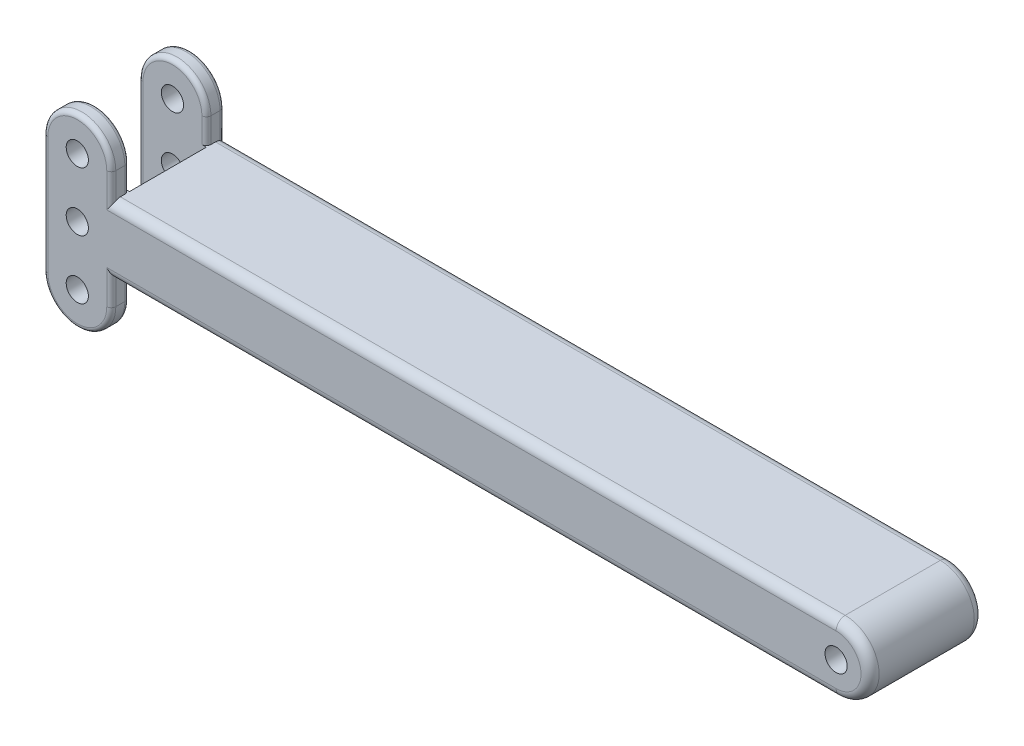
SolidWorks part; units mm, degrees
ref_plane "Front Plane" through (0, 0, 0) normal (0, 0, 1) x (1, 0, 0)
ref_plane "Top Plane" through (0, 0, 0) normal (0, 1, 0) x (1, 0, 0)
ref_plane "Right Plane" through (0, 0, 0) normal (1, 0, 0) x (0, 0, -1)
sketch "Sketch1" plane through (0, 0, 0) normal (0, 0, 1) x (1, 0, 0)
  line L0 (0, 0) -> (0, 33.02) construction
  line L1 (-9.525, 0) -> (-9.525, 33.02)
  line L2 (9.525, 0) -> (9.525, 33.02)
  line L3 (9.525, 26.035) -> (212.725, 26.035)
  line L4 (9.525, 6.985) -> (212.725, 6.985)
  line L5 (0, 16.51) -> (9.525, 26.035) construction
  line L6 (0, 16.51) -> (9.525, 6.985) construction
  arc A0 (-9.525, 0) -> (9.525, 0) centre (0, 0) ccw
  arc A1 (9.525, 33.02) -> (-9.525, 33.02) centre (0, 33.02) ccw
  arc A2 (212.725, 26.035) -> (212.725, 6.985) centre (212.725, 16.51) cw
  circle A3 centre (0, 33.02) radius 3.1115
  circle A4 centre (0, 0) radius 3.1115
  circle A5 centre (0, 16.51) radius 3.1115
  circle A6 centre (212.725, 16.51) radius 3.1115
  point P3 (0, 16.51)
  point P17 (9.525, 16.51)
  dimension "D1" = 9.525
  dimension "D5" = 6.223
  dimension "D4" = 6.223
  dimension "D7" = 6.223
  dimension "D2" = 33.02
  dimension "D3" = 19.05
  dimension "D6" = 203.2
extrude "Boss-Extrude1" add sketch "Sketch1" along normal blind 31.75 contours A2 L3 L2 L4 | L2 A1 L1 A0 A4 A3 region at (-8.9705, 16.51, 0) region at (114.129, 16.51, 0)
sketch "Sketch2" plane through (-9.525, 0, 0) normal (-1, 0, 0) x (0, 0, 1)
  line L0 (0, 0) -> (0, -9.525) construction
  line L1 (0, 0) -> (31.75, 0) construction
  line L2 (31.75, -9.525) -> (31.75, 0) construction
  line L3 (0, 42.545) -> (0, 33.02) construction
  line L4 (31.75, 33.02) -> (31.75, 42.545) construction
  line L5 (31.75, 33.02) -> (0, 33.02) construction
  line L6 (0, 33.02) -> (0, 0) construction
  line L7 (31.75, 0) -> (31.75, 33.02) construction
  line L8 (0, 0) -> (0, -9.525)
  line L9 (0, 0) -> (31.75, 0)
  line L10 (31.75, -9.525) -> (31.75, 0)
  line L11 (0, 42.545) -> (0, 33.02)
  line L12 (31.75, 33.02) -> (31.75, 42.545)
  line L13 (31.75, 33.02) -> (0, 33.02)
  line L14 (0, 33.02) -> (0, 0)
  line L15 (31.75, 0) -> (31.75, 33.02)
  line L16 (31.75, 42.545) -> (0, 42.545) construction
  line L17 (5.08, 42.545) -> (26.67, 42.545)
  line L18 (5.08, 42.545) -> (5.08, -9.525)
  line L19 (5.08, -9.525) -> (26.67, -9.525)
  line L20 (26.67, 42.545) -> (26.67, -9.525)
  line L21 (0, -9.525) -> (31.75, -9.525) construction
  line L26 (15.875, 0) -> (15.875, 50000) construction
  point P20 (15.875, 42.545)
  point P29 (15.875, 0)
  line M7 (0, 0) -> (31.75, 0)
  line M9 (31.75, 33.02) -> (0, 33.02)
  dimension "D1" = 21.59
extrude "Cut-Extrude1" cut sketch "Sketch2" against normal blind 19.05 contours L9 L26 L18 M9 | L26 L20 L13 M7 | L26 L17 L18 M9 | L26 L13 L20 L17 | L19 L26 L9 L18 | L26 L19 L20 M7 region at (-9.525, 16.51, 10.4775) region at (-9.525, -4.7625, 15.875) region at (-9.525, 16.51, 21.2725) region at (-9.525, 37.7825, 10.4775) region at (-9.525, 37.7825, 21.2725)
fillet "Fillet1" radius 2.54 6 edges at (111.125, 26.035, 0) (222.25, 16.51, 0) (111.125, 26.035, 31.75) (222.25, 16.51, 31.75) (111.125, 6.985, 0) (111.125, 6.985, 31.75)
fillet "Fillet2" radius 1.27 20 edges at (9.525, 3.4925, 26.67) (9.525, 29.5275, 26.67) (0, 42.545, 26.67) (-9.525, 16.51, 26.67) (9.525, 28.2575, 0) (0, 42.545, 0) (-9.525, 16.51, 0) (9.525, 4.7625, 0) (9.525, 3.4925, 5.08) (9.525, 29.5275, 5.08) (0, 42.545, 5.08) (-9.525, 16.51, 5.08) (9.525, 28.2575, 31.75) (0, 42.545, 31.75) (-9.525, 16.51, 31.75) (9.525, 4.7625, 31.75) (0, -9.525, 26.67) (0, -9.525, 0) (0, -9.525, 5.08) (0, -9.525, 31.75)
